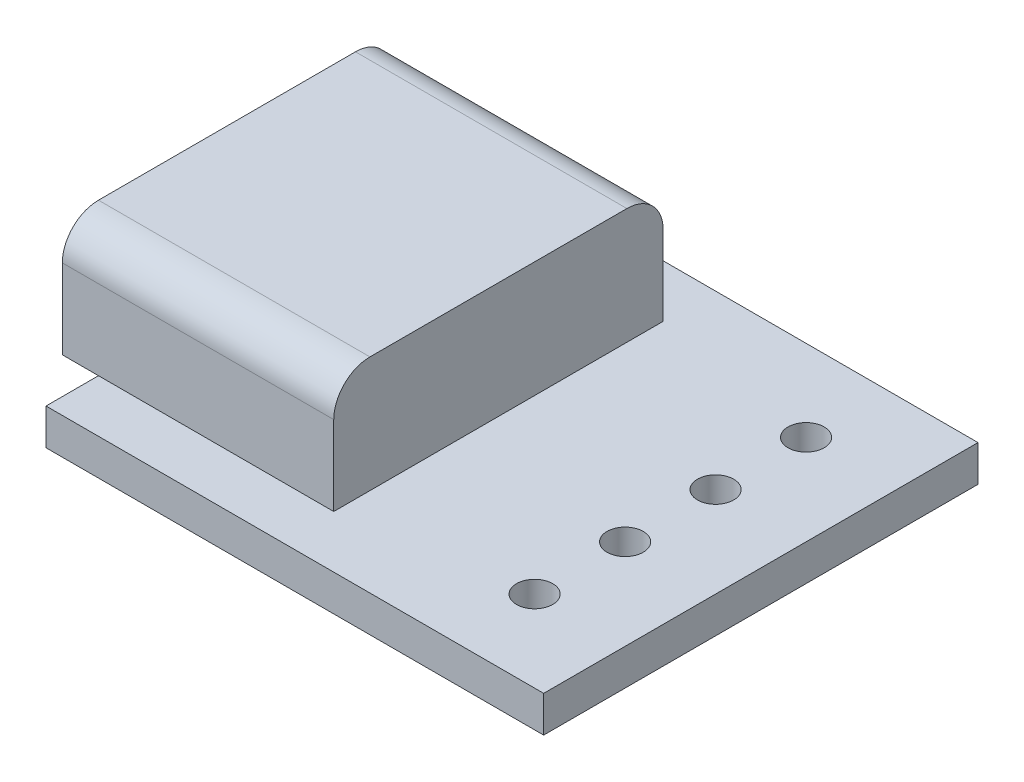
SolidWorks part; units mm, degrees
ref_plane "Front Plane" through (0, 0, 0) normal (0, 0, 1) x (1, 0, 0)
ref_plane "Top Plane" through (0, 0, 0) normal (0, 1, 0) x (1, 0, 0)
ref_plane "Right Plane" through (0, 0, 0) normal (1, 0, 0) x (0, 0, -1)
sketch "Sketch1" plane through (0, 0, 0) normal (0, 1, 0) x (1, 0, 0)
  line L0 (11.25, 12) -> (11.25, 0) construction
  line L1 (0, 0) -> (13.75, 0)
  line L2 (0, 0) -> (0, 12)
  line L3 (0, 12) -> (13.75, 12)
  line L4 (13.75, 0) -> (13.75, 12)
  line L5 (11.75, 9.75) -> (11.75, 10.25) construction
  line L6 (11.25, 10.25) -> (11.75, 10.25) construction
  line L7 (11.25, 9.75) -> (11.25, 7.25) construction
  line L8 (0, 6) -> (13.75, 6) construction
  line L9 (6.5, 10.55) -> (-1, 10.55)
  line L10 (6.5, 10.55) -> (6.5, 1.45)
  line L11 (6.5, 1.45) -> (-1, 1.45)
  line L12 (-1, 10.55) -> (-1, 1.45)
  line L13 (2.75, 1.45) -> (2.75, 10.55) construction
  line L14 (6.5, 6) -> (-1, 6) construction
  circle A0 centre (11.25, 9.75) radius 0.5
  circle A1 centre (11.25, 7.25) radius 0.5
  circle A2 centre (11.25, 4.75) radius 0.5
  circle A3 centre (11.25, 2.25) radius 0.5
  point P10 (2.75, 6)
  dimension "D4" = 1
  dimension "D1" = 13.75
  dimension "D2" = 12
  dimension "D3" = 2
  dimension "D5" = 1.75
  dimension "D7" = 2.5
  dimension "D8" = 9.1
  dimension "D9" = 7.25
  dimension "D10" = 7.5
  dimension "D6" = 4
extrude "Boss-Extrude1" add sketch "Sketch1" along normal blind 1 contours L10 L11 L2 L1 L4 L3 L9 A3 A2 A1 A0 | L11 L10 L9 L2 region at (8.8288, 0, -6) region at (3.25, 0, -6)
extrude "Boss-Extrude2" add sketch "Sketch1<3>" along normal blind 3.2 from surface contours L9 L12 L11 L2 | L11 L10 L9 L2 region at (-0.5, 0, -6) region at (3.25, 0, -6) starting at face at (6.875, 1, -6)
sketch "Sketch1<3>" plane through (0, 0, 0) normal (0, 1, 0) x (1, 0, 0) same geometry as "Sketch1"
fillet "Fillet1" radius 1 2 edges at (2.75, 4.2, -1.45) (2.75, 4.2, -10.55)
